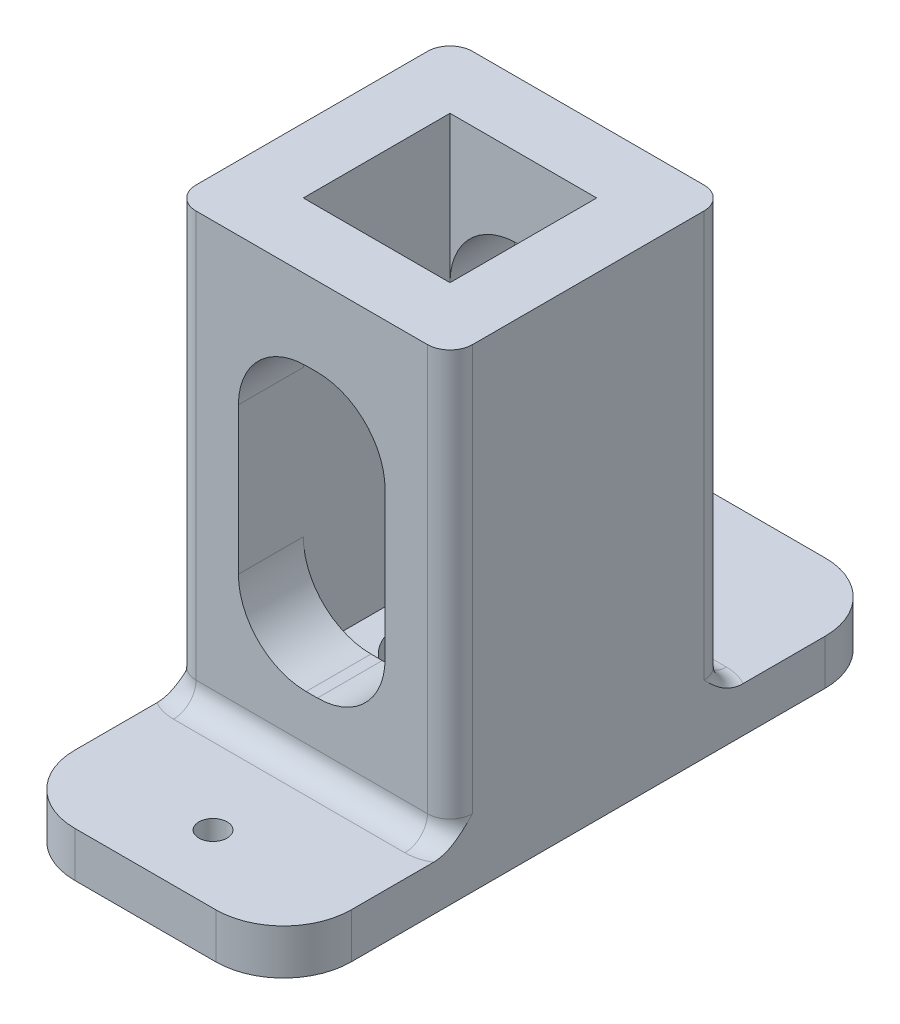
SolidWorks part; units mm, degrees
material "PBT Общее назначение"
ref_plane "Спереди" through (0, 0, 0) normal (0, 0, 1) x (1, 0, 0)
ref_plane "Сверху" through (0, 0, 0) normal (0, 1, 0) x (1, 0, 0)
ref_plane "Справа" through (0, 0, 0) normal (1, 0, 0) x (0, 0, -1)
sketch "Эскиз1" plane through (0, 0, 0) normal (0, 1, 0) x (1, 0, 0)
  line L0 (0, 0) -> (24.5, 0)
  line L1 (0, 0) -> (0, 24.5)
  line L2 (24.5, 0) -> (24.5, 24.5)
  line L3 (0, 24.5) -> (24.5, 24.5)
  dimension "D1" = 24.5
  dimension "D2" = 24.5
extrude "Бобышка-Вытянуть1" add sketch "Эскиз1" along normal blind 38
sketch "Эскиз2" plane through (0, 0, 0) normal (0, -1, 0) x (1, 0, 0)
  line L0 (24.5, -24.5) -> (24.5, -33.25)
  line L1 (18.5, -39.25) -> (6, -39.25)
  line L2 (0, -33.25) -> (0, -24.5)
  line L3 (0, -24.5) -> (0, 0) construction
  line L4 (0, -24.5) -> (0, 0)
  line L6 (0, 0) -> (0, 8.75)
  line L7 (6, 14.75) -> (18.5, 14.75)
  line L8 (24.5, 8.75) -> (24.5, 0)
  line L9 (24.5, 0) -> (24.5, -24.5)
  line L10 (24.5, -24.5) -> (0, -24.5) construction
  arc A2 (0, -33.25) -> (6, -39.25) centre (6, -33.25) ccw
  arc A3 (18.5, -39.25) -> (24.5, -33.25) centre (18.5, -33.25) ccw
  arc A4 (24.5, 8.75) -> (18.5, 14.75) centre (18.5, 8.75) ccw
  arc A5 (6, 14.75) -> (0, 8.75) centre (6, 8.75) ccw
  point P34 (0, 0)
  dimension "D2" = 6
  dimension "D1" = 14.75
extrude "Бобышка-Вытянуть2" add sketch "Эскиз2" along normal blind 4
sketch "Эскиз3" plane through (0, 38, 0) normal (0, 1, 0) x (1, 0, 0)
  line L0 (24.5, 12.25) -> (0, 12.25) construction
  line L1 (24.5, 0) -> (24.5, 24.5) construction
  line L2 (0, 24.5) -> (0, 0) construction
  line L3 (12.25, 0) -> (12.25, 24.5) construction
  line L4 (0, 0) -> (24.5, 0) construction
  line L5 (24.5, 24.5) -> (0, 24.5) construction
  line L6 (18.75, 5.75) -> (5.75, 5.75)
  line L7 (18.75, 5.75) -> (18.75, 18.75)
  line L8 (5.75, 5.75) -> (5.75, 18.75)
  line L9 (18.75, 18.75) -> (5.75, 18.75)
  point P12 (5.75, 12.25)
  point P15 (12.25, 5.75)
  dimension "D1" = 13
extrude "Вырез-Вытянуть1" cut sketch "Эскиз3" against normal blind 35
sketch "Эскиз4" plane through (0, 3, 0) normal (0, 1, 0) x (1, 0, 0)
  line L0 (12.25, 5.75) -> (12.25, 18.75) construction
  line L1 (5.75, 5.75) -> (18.75, 5.75) construction
  line L2 (18.75, 18.75) -> (5.75, 18.75) construction
  line L3 (12.25, 12.25) -> (5.75, 12.25) construction
  line L6 (5.75, 18.75) -> (5.75, 5.75) construction
  line L7 (12.25, 12.25) -> (18.75, 12.25) construction
  line L8 (18.75, 5.75) -> (18.75, 18.75) construction
  circle A0 centre (12.25, 12.25) radius 4.5
  dimension "D1" = 9
extrude "Вырез-Вытянуть2" cut sketch "Эскиз4" against normal through all
sketch "Эскиз5" plane through (0, 0, 0) normal (0, 0, 1) x (1, 0, 0)
  line L0 (12.25, 38) -> (12.25, 3) construction
  line L1 (11.75, 31) -> (12.75, 31)
  line L2 (5.75, 25) -> (5.75, 12)
  line L3 (18.75, 25) -> (18.75, 12)
  line L4 (18.75, 38) -> (5.75, 38)
  line L5 (18.75, 3) -> (18.75, 38)
  line L6 (5.75, 3) -> (18.75, 3)
  line L7 (5.75, 38) -> (5.75, 3)
  line L8 (18.75, 38) -> (5.75, 38) construction
  line L9 (18.75, 3) -> (18.75, 38) construction
  line L10 (5.75, 3) -> (18.75, 3) construction
  line L11 (5.75, 38) -> (5.75, 3) construction
  line L12 (11.75, 6) -> (12.75, 6)
  arc A0 (18.75, 12) -> (12.75, 6) centre (12.75, 12) cw
  arc A1 (11.75, 6) -> (5.75, 12) centre (11.75, 12) cw
  arc A2 (18.75, 25) -> (12.75, 31) centre (12.75, 25) ccw
  arc A3 (5.75, 25) -> (11.75, 31) centre (11.75, 25) cw
  point P6 (12.25, 31)
  dimension "D4" = 6
  dimension "D2" = 25
  dimension "D3" = 7
  dimension "D1" = 0
extrude "Вырез-Вытянуть3" cut sketch "Эскиз5" against normal through all
fillet "Скругление1" radius 2 4 edges
sketch "Эскиз6" plane through (0, -4, 0) normal (0, -1, 0) x (1, 0, 0)
  line L0 (12.25, 14.75) -> (12.25, -39.25) construction
  line L1 (18.5, 14.75) -> (6, 14.75) construction
  line L2 (6, -39.25) -> (18.5, -39.25) construction
  line L3 (0, -12.25) -> (24.5, -12.25) construction
  line L5 (24.5, -33.25) -> (24.5, 8.75) construction
  line L6 (6, -39.25) -> (18.5, -39.25) construction
  line L7 (18.5, 14.75) -> (6, 14.75) construction
  line L8 (0, 8.75) -> (0, -33.25) construction
  circle A0 centre (12.25, 8.75) radius 1.25
  circle A1 centre (12.25, -32.25) radius 1.25
  dimension "D3" = 7
  dimension "D4" = 2.5
  dimension "D6" = 2.5
  dimension "D5" = 6
extrude "Вырез-Вытянуть4" cut sketch "Эскиз6" against normal through all
fillet "Скругление2" radius 2 6 edges at (23.9142, 0, -23.9142) (0.5858, 0, -23.9142) (0.5858, 0, -0.5858) (23.9142, 0, -0.5858)
sketch "Эскиз7" plane through (0, 38, 0) normal (0, 1, 0) x (1, 0, 0)
  line L0 (0, 12.25) -> (24.5, 12.25) construction
  line L1 (0, 22.5) -> (0, 2) construction
  line L2 (24.5, 2) -> (24.5, 22.5) construction
ref_plane "Плоскость1" through (0, 0, -12.25) normal (0, 0, 1) x (1, 0, 0)
